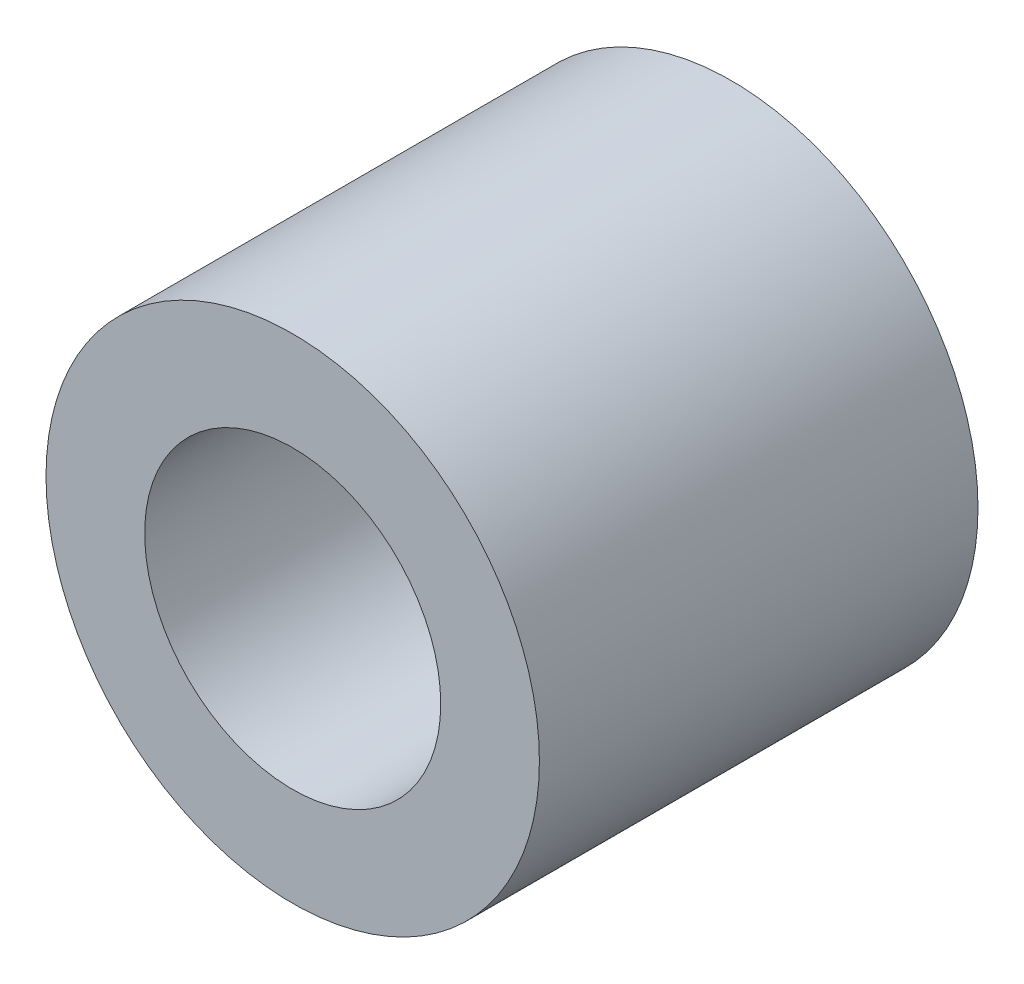
SolidWorks part; units mm, degrees
ref_plane "Front Plane" through (0, 0, 0) normal (0, 0, 1) x (1, 0, 0)
ref_plane "Top Plane" through (0, 0, 0) normal (0, 1, 0) x (1, 0, 0)
ref_plane "Right Plane" through (0, 0, 0) normal (1, 0, 0) x (0, 0, -1)
sketch "Sketch1" plane through (0, 0, 0) normal (0, 0, 1) x (1, 0, 0)
  circle A0 centre (0, 0) radius 2.25
  circle A1 centre (0, 0) radius 1.35
  dimension "OD" = 4.5
  dimension "ID" = 2.7
extrude "Extrude1" add sketch "Sketch1" along normal mid plane 4
sketch "Sketch2" plane through (0, 0, 0) normal (1, 0, 0) x (0, 0, -1)
  line L0 (-2, -1.35) -> (2, -1.35) construction
  line L3 (2, 1.35) -> (-2, 1.35) construction
  line L5 (-2, -1.35) -> (2, -1.35)
  line L6 (2, 1.35) -> (-2, 1.35)
sketch "Sketch4" plane through (0, 0, 2) normal (0, 0, 1) x (1, 0, 0)
  line L0 (0, 0) -> (-0.9546, 0.9546)
  line L1 (0, -1.1) -> (0, 1.1) construction
  circle A0 centre (0, 0) radius 1.35 construction
  dimension "D1" = 45
